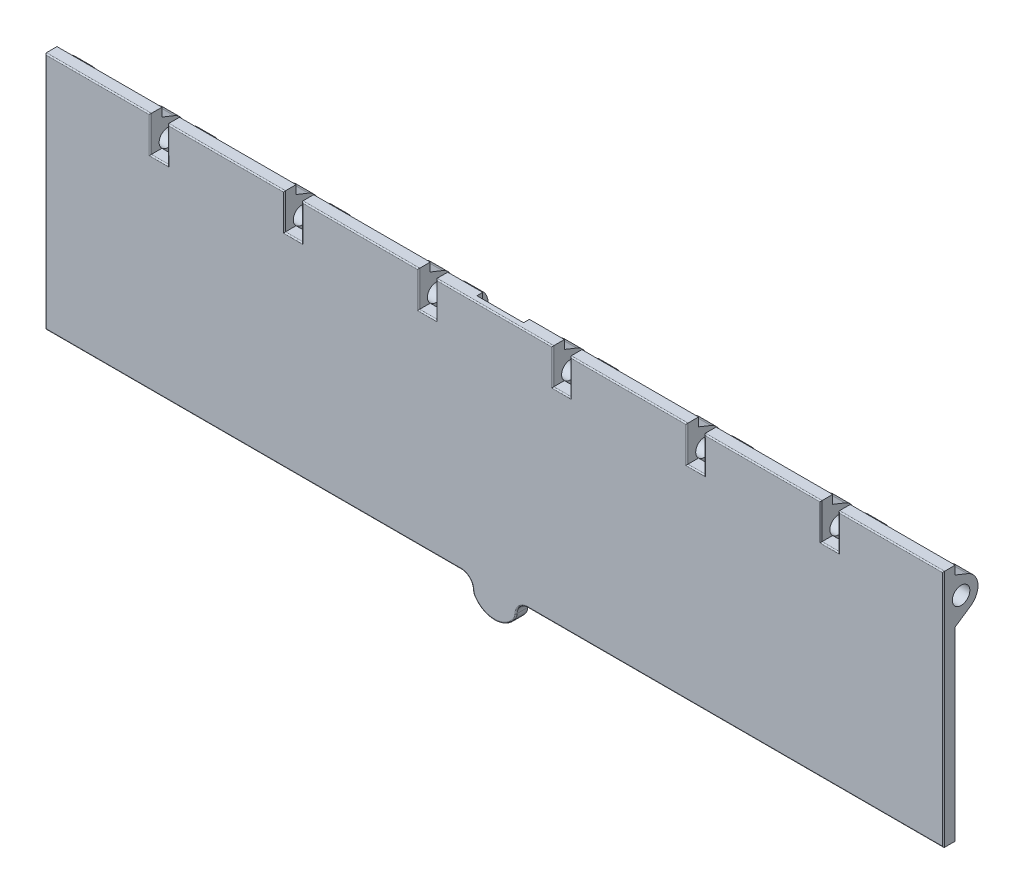
SolidWorks part; units mm, degrees
ref_plane "Front Plane" through (0, 0, 0) normal (0, 0, 1) x (1, 0, 0)
ref_plane "Top Plane" through (0, 0, 0) normal (0, 1, 0) x (1, 0, 0)
ref_plane "Right Plane" through (0, 0, 0) normal (1, 0, 0) x (0, 0, -1)
sketch "Sketch1" plane through (0, 0, 0) normal (0, 0, 1) x (1, 0, 0)
  line L0 (-31, -12) -> (-31, -53)
  line L5 (-31, -53) -> (123, -53)
  line L6 (123, -12) -> (123, -53)
  line L7 (-31, -12) -> (123, -12)
extrude "Boss-Extrude1" add sketch "Sketch1" along normal up to surface (2 mm away)
sketch "Sketch2" plane through (-31, 0, 0) normal (-1, 0, 0) x (0, 0, 1)
  line L3 (2, -12) -> (0, -12) construction
  line L4 (-1, -44.5) -> (-1, -12.2142) construction
  circle A1 centre (-1, -17) radius 1.5
  dimension "D4" = 3
  dimension "D5" = 5
extrude "Cut-Extrude1" cut sketch "Sketch2" against normal blind 204
sketch "Sketch3" plane through (-31, 0, 0) normal (-1, 0, 0) x (0, 0, 1)
  line L0 (0.5, -17) -> (-2.5345, -17) construction
  line L1 (-2.6395, -19.4038) -> (0, -21.1852)
  line L2 (0, -18.118) -> (0, -53) construction
  line L3 (-2.0925, -14.3067) -> (0, -13.4713)
  line L4 (0, -12) -> (0, -15.882) construction
  line L5 (0, -13.4713) -> (0, -14.2843)
  line L6 (0, -21.1852) -> (0, -19.7157)
  arc A0 (0, -18.118) -> (0, -15.882) centre (-1, -17) ccw construction
  circle A1 centre (-1.0173, -17) radius 1.5
  arc A2 (0, -19.7157) -> (0, -14.2843) centre (-1.0173, -17) ccw
  circle A3 centre (-1.0173, -17) radius 2.9 construction
  arc A4 (-2.0925, -14.3067) -> (-2.6395, -19.4038) centre (-1.0173, -17) ccw
  dimension "D1" = 3
  dimension "D2" = 1.4
extrude "Boss-Extrude2" add sketch "Sketch3" against normal up to surface (154 mm away) up to face at (123, -27.3333, 0.75)
sketch "Sketch4" plane through (0, 0, 0) normal (0, 0, -1) x (-1, 0, 0)
  line L0 (-123, -21.1852) -> (-120, -21.1852) construction
  line L1 (31, -21.1852) -> (28, -21.1852) construction
  line L27 (28, -21.1852) -> (16, -21.1852)
  line L36 (28, -21.1852) -> (28, 1.9762)
  line L37 (-123, -21.1852) -> (31, -21.1852) construction
  line L38 (-82, -21.1852) -> (-82, -2.5423)
  line L39 (-120, -21.1852) -> (-108, -21.1852)
  line L40 (-120, -21.1852) -> (-120, -6.4019)
  line L41 (-120, -6.4019) -> (-108, -6.4019)
  line L42 (-108, -21.1852) -> (-108, -6.4019)
  line L43 (-105, -21.1852) -> (-102, -21.1852)
  line L44 (-105, -21.1852) -> (-105, -2.5423)
  line L45 (-105, -2.5423) -> (-102, -2.5423)
  line L46 (-102, -21.1852) -> (-102, -2.5423)
  line L47 (-99, -21.1852) -> (-85, -21.1852)
  line L48 (-99, -21.1852) -> (-99, -3.5866)
  line L49 (-99, -3.5866) -> (-85, -3.5866)
  line L50 (-85, -21.1852) -> (-85, -3.5866)
  line L51 (-82, -21.1852) -> (-79, -21.1852)
  line L52 (-79, -21.1852) -> (-79, -2.5423)
  line L53 (-82, -2.5423) -> (-79, -2.5423)
  line L54 (-76, -21.1852) -> (-76, -3.5866)
  line L55 (-76, -21.1852) -> (-62, -21.1852)
  line L56 (-62, -21.1852) -> (-62, -3.5866)
  line L57 (-76, -3.5866) -> (-62, -3.5866)
  line L58 (-59, -21.1852) -> (-59, -2.5423)
  line L59 (-59, -21.1852) -> (-56, -21.1852)
  line L60 (-56, -21.1852) -> (-56, -2.5423)
  line L61 (-59, -2.5423) -> (-56, -2.5423)
  line L62 (-53, -21.1852) -> (-53, -3.5866)
  line L63 (-53, -21.1852) -> (-39, -21.1852)
  line L64 (-39, -21.1852) -> (-39, -3.5866)
  line L65 (-53, -3.5866) -> (-39, -3.5866)
  line L66 (-36, -21.1852) -> (-36, -2.5423)
  line L67 (-36, -21.1852) -> (-33, -21.1852)
  line L68 (-33, -21.1852) -> (-33, -2.5423)
  line L69 (-36, -2.5423) -> (-33, -2.5423)
  line L70 (-30, -21.1852) -> (-30, -3.5866)
  line L71 (-30, -21.1852) -> (-16, -21.1852)
  line L72 (-16, -21.1852) -> (-16, -3.5866)
  line L73 (-30, -3.5866) -> (-16, -3.5866)
  line L74 (-13, -21.1852) -> (-13, -2.5423)
  line L75 (-13, -21.1852) -> (-10, -21.1852)
  line L76 (-10, -21.1852) -> (-10, -2.5423)
  line L77 (-13, -2.5423) -> (-10, -2.5423)
  line L78 (-7, -21.1852) -> (-7, -3.5866)
  line L79 (-7, -21.1852) -> (7, -21.1852)
  line L80 (7, -21.1852) -> (7, -3.5866)
  line L81 (-7, -3.5866) -> (7, -3.5866)
  line L82 (28, 1.9762) -> (16, 1.9762)
  line L83 (16, -21.1852) -> (16, 1.9762)
  line L84 (13, -21.1852) -> (10, -21.1852)
  line L85 (13, -21.1852) -> (13, 6.619)
  line L86 (13, 6.619) -> (10, 6.619)
  line L87 (10, -21.1852) -> (10, 6.619)
  dimension "D1" = 3
  dimension "D2" = 12
  dimension "D3" = 3
  dimension "D4" = 3
  dimension "D6" = 3
  dimension "D7" = 5
  dimension "D8" = 3
  dimension "D5" = 14
  dimension "D9" = 12
  dimension "D10" = 3
  dimension "D11" = 3
extrude "Cut-Extrude2" cut sketch "Sketch4" along normal blind 204
sketch "Sketch5" plane through (0, 0, 0) normal (0, 0, -1) x (-1, 0, 0)
  line L0 (-82, -18.1024) -> (-82, -4.7862)
  line L1 (-105, -18.1024) -> (-102, -18.1024)
  line L2 (-105, -18.1024) -> (-105, -4.7862)
  line L3 (-105, -4.7862) -> (-102, -4.7862)
  line L4 (-102, -18.1024) -> (-102, -4.7862)
  line L5 (-82, -18.1024) -> (-79, -18.1024)
  line L6 (-79, -18.1024) -> (-79, -4.7862)
  line L7 (-82, -4.7862) -> (-79, -4.7862)
  line L8 (-59, -18.1024) -> (-59, -4.7862)
  line L9 (-59, -18.1024) -> (-56, -18.1024)
  line L10 (-56, -18.1024) -> (-56, -4.7862)
  line L11 (-59, -4.7862) -> (-56, -4.7862)
  line L12 (-36, -18.1024) -> (-36, -4.7862)
  line L13 (-36, -18.1024) -> (-33, -18.1024)
  line L14 (-33, -18.1024) -> (-33, -4.7862)
  line L15 (-36, -4.7862) -> (-33, -4.7862)
  line L16 (-13, -18.1024) -> (-13, -4.7862)
  line L17 (-13, -18.1024) -> (-10, -18.1024)
  line L18 (-10, -18.1024) -> (-10, -4.7862)
  line L19 (-13, -4.7862) -> (-10, -4.7862)
  line L20 (10, -18.1024) -> (10, -4.7862)
  line L21 (10, -18.1024) -> (13, -18.1024)
  line L22 (13, -18.1024) -> (13, -4.7862)
  line L23 (10, -4.7862) -> (13, -4.7862)
  dimension "D1" = 3
  dimension "D2" = 6
extrude "Cut-Extrude3" cut sketch "Sketch5" against normal blind 5
sketch "Sketch6" plane through (0, 0, 0) normal (0, 0, -1) x (-1, 0, 0)
  line L0 (-46, -18.1024) -> (-46, -48.4041) construction
  line L1 (-39, -18.1024) -> (-53, -18.1024) construction
  line L2 (-56, -12) -> (-36, -12) construction
  line L3 (-50, -12) -> (-42, -12)
  line L4 (-50, -12) -> (-50, -46.5676)
  line L5 (-50, -46.5676) -> (-42, -46.5676)
  line L6 (-42, -12) -> (-42, -46.5676)
  dimension "D1" = 8
  dimension "D2" = 4
  dimension "D3" = 34.5676
extrude "Cut-Extrude4" cut sketch "Sketch6" against normal blind 1
sketch "Sketch7" plane through (0, 0, 0) normal (0, 0, -1) x (-1, 0, 0)
  line L15 (-51.368, -22.3728) -> (-40.9511, -22.3728)
  line L16 (-51.368, -22.3728) -> (-51.368, -47.533)
  line L17 (-51.368, -47.533) -> (-40.9511, -47.533)
  line L18 (-40.9511, -22.3728) -> (-40.9511, -47.533)
extrude "Boss-Extrude3" add sketch "Sketch7" along normal blind 1
fillet "Fillet1" radius 10 3 edges at (40.9511, -34.9529, -1) (51.368, -34.9529, -1) (46.1596, -47.533, -1)
sketch "Sketch8" plane through (0, 0, 2) normal (0, 0, 1) x (1, 0, 0)
  line L0 (46, -12) -> (46, -53) construction
  line L1 (36, -12) -> (56, -12) construction
  line L2 (123, -53) -> (-31, -53) construction
  line L3 (42.2873, -53) -> (49.7264, -53)
  line L4 (42.2873, -53) -> (42.2873, -55.335)
  line L6 (49.7264, -55.335) -> (49.7264, -53)
  arc A1 (42.2873, -55.335) -> (49.7264, -55.335) centre (46.0068, -53.599) ccw
extrude "Boss-Extrude4" add sketch "Sketch8" against normal up to surface (2 mm away) up to face at (46.01, -21.7283, 0)
fillet "Fillet2" radius 2 2 edges at (42.2873, -53, 1) (49.7264, -53, 1)
fillet "Fillet3" radius 2 2 edges at (42.2873, -55.335, 1) (49.7264, -55.335, 1)
fillet "Fillet4" radius 0.2 34 edges at (4.6436, -53, 2) (-31, -32.5, 2) (-22, -12, 2) (-13, -15.0512, 2) (-11.5, -18.1024, 2) (-10, -15.0512, 2) (0, -12, 2) (10, -15.0512, 2) (11.5, -18.1024, 2) (13, -15.0512, 2) (23, -12, 2) (33, -15.0512, 2) (34.5, -18.1024, 2) (36, -15.0512, 2) (46, -12, 2) (56, -15.0512, 2) (57.5, -18.1024, 2) (59, -15.0512, 2) (69, -12, 2) (79, -15.0512, 2) (80.5, -18.1024, 2) (82, -15.0512, 2) (92, -12, 2) (102, -15.0512, 2) (103.5, -18.1024, 2) (105, -15.0512, 2) (114, -12, 2) (123, -32.5, 2) (87.3632, -53, 2) (50.3469, -53.5519, 2) (49.6235, -55.4534, 2) (46.0068, -57.7038, 2) (42.3902, -55.4534, 2) (41.6667, -53.5519, 2)
